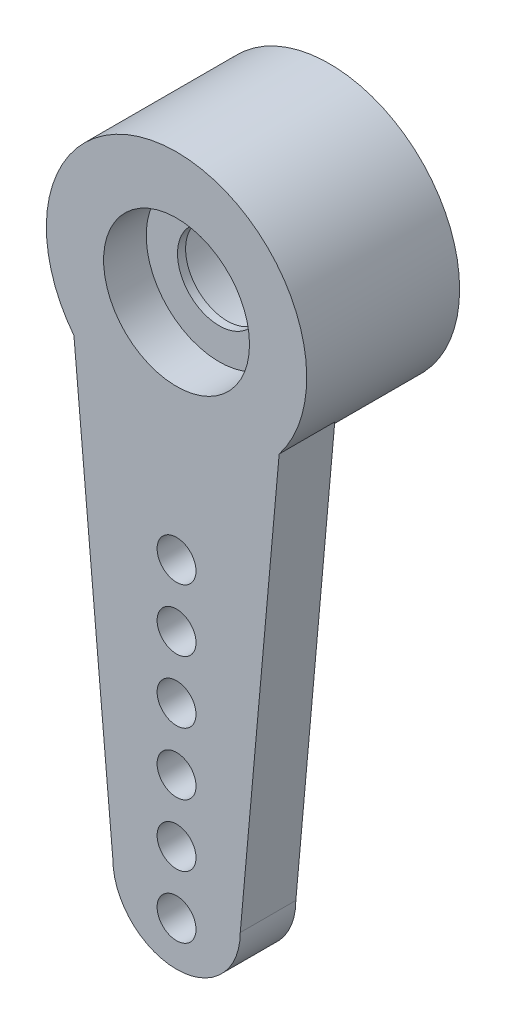
SolidWorks part; units mm, degrees
material "Nylon 6/10"
ref_plane "Front Plane" through (0, 0, 0) normal (0, 0, 1) x (1, 0, 0)
ref_plane "Top Plane" through (0, 0, 0) normal (0, 1, 0) x (1, 0, 0)
ref_plane "Right Plane" through (0, 0, 0) normal (1, 0, 0) x (0, 0, -1)
ref_plane "Plane1" through (0, 0, -7.033) normal (0, 0, 1) x (1, 0, 0)
sketch "Sketch1" plane through (0, 0, -7.033) normal (0, 0, 1) x (1, 0, 0)
  circle A0 centre (-5.5, 0) radius 3.5687
  circle A1 centre (-5.5, 0) radius 2
  dimension "D1" = 7.1374
extrude "Boss-Extrude1" add sketch "Sketch1" along normal blind 4.191
sketch "Sketch5" plane through (0, 0, -4.233) normal (0, 0, 1) x (1, 0, 0)
  circle A0 centre (-5.5, 0) radius 1.143
  circle A1 centre (-5.5, 0) radius 2 construction
  circle A2 centre (-5.5, 0) radius 2
  dimension "D1" = 2.286
extrude "Boss-Extrude2" add sketch "Sketch5" along normal offset from surface (0.2226 mm away) 1.1684 up to face at (-1.9313, 0, -2.842)
sketch "Sketch6" plane through (0, 0, -2.842) normal (0, 0, 1) x (1, 0, 0)
  line L0 (-3.7537, -14.0907) -> (-2.6869, -2.196)
  line L1 (-7.2462, -14.0907) -> (-8.313, -2.196)
  line L2 (-5.5, 0) -> (-5.5, -14.0907) construction
  line L3 (-5.5, -14.6241) -> (-5.5, -12.9223) construction
  arc A0 (-7.2462, -14.0907) -> (-3.7537, -14.0907) centre (-5.5, -14.0907) ccw
  circle A1 centre (-5.5, 0) radius 3.5687 construction
  circle A2 centre (-5.5, 0) radius 3.5687 construction
  circle A3 centre (-5.5, -12.9223) radius 0.5334
  circle A4 centre (-5.5, -14.6241) radius 0.5334
  circle A5 centre (-5.5, -11.2205) radius 0.5334
  circle A6 centre (-5.5, -9.5186) radius 0.5334
  circle A7 centre (-5.5, -7.8169) radius 0.5334
  circle A8 centre (-5.5, -6.1151) radius 0.5334
  arc A9 (-2.6869, -2.196) -> (-8.313, -2.196) centre (-5.5, 0) cw
  dimension "D1" = 3.4925
  dimension "D2" = 15.8369
  dimension "D4" = 1.0668
  dimension "D3" = 5.6261
  dimension "D6" = 1.7018
  dimension "D5" = 6
extrude "Boss-Extrude3" add sketch "Sketch6" against normal blind 1.524
move or copy body "Body-Move/Copy1" [suppressed] bodies to move or copy 103
